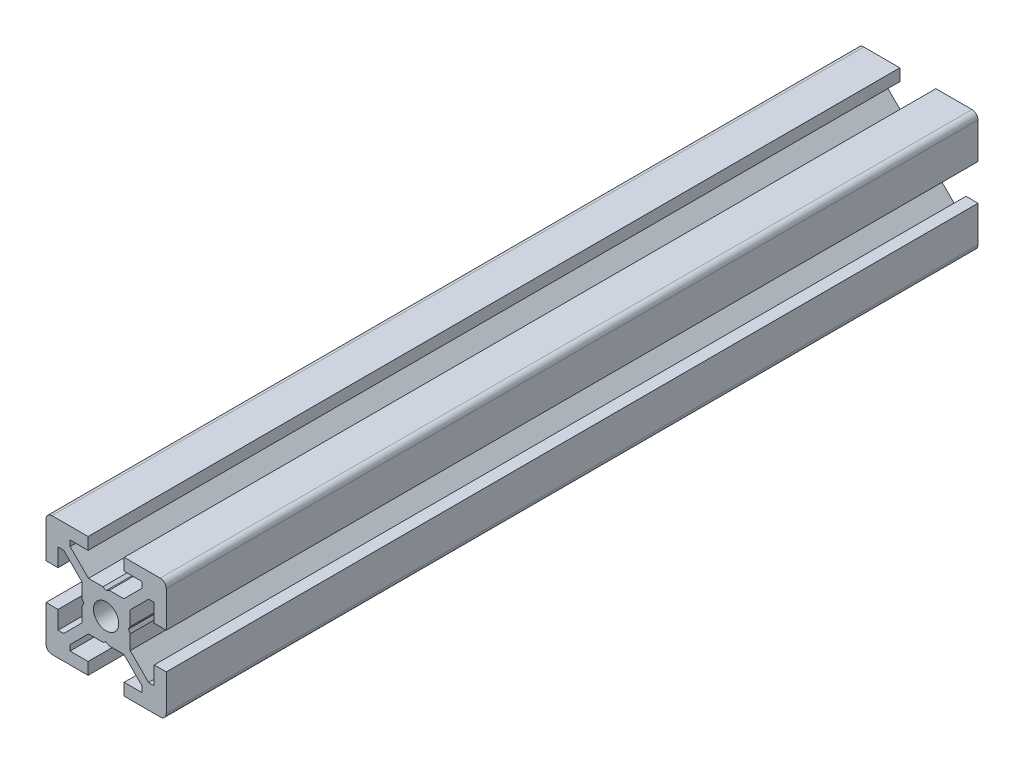
SolidWorks part; units mm, degrees
ref_plane "Front Plane" through (0, 0, 0) normal (0, 0, 1) x (1, 0, 0)
ref_plane "Top Plane" through (0, 0, 0) normal (0, 1, 0) x (1, 0, 0)
ref_plane "Right Plane" through (0, 0, 0) normal (1, 0, 0) x (0, 0, -1)
ref_plane "Plane1" through (0, 0, 0) normal (0, 0, 1) x (1, 0, 0)
sketch "Sketch1" plane through (0, 0, 0) normal (0, 0, 1) x (1, 0, 0)
  line L0 (-10, -3) -> (-10, -9)
  line L1 (-9, -10) -> (-3, -10)
  line L2 (-3, -10) -> (-3, -8)
  line L3 (-3, -8) -> (-6, -8)
  line L4 (-6, -8) -> (-6, -7.0607)
  line L5 (-6, -7.0607) -> (-2.9393, -4)
  line L6 (-2.9393, -4) -> (-0.5196, -4)
  line L7 (-0.5196, -4) -> (0, -3.7)
  line L8 (0, -3.7) -> (0.5196, -4)
  line L9 (0.5196, -4) -> (2.9393, -4)
  line L10 (2.9393, -4) -> (6, -7.0607)
  line L11 (6, -7.0607) -> (6, -8)
  line L12 (6, -8) -> (3, -8)
  line L13 (3, -8) -> (3, -10)
  line L14 (3, -10) -> (9, -10)
  line L15 (10, -9) -> (10, -3)
  line L16 (10, -3) -> (8, -3)
  line L17 (8, -3) -> (8, -6)
  line L18 (8, -6) -> (7.0607, -6)
  line L19 (7.0607, -6) -> (4, -2.9393)
  line L20 (4, -2.9393) -> (4, -0.5196)
  line L21 (4, -0.5196) -> (3.7, 0)
  line L22 (3.7, 0) -> (4, 0.5196)
  line L23 (4, 0.5196) -> (4, 2.9393)
  line L24 (4, 2.9393) -> (7.0607, 6)
  line L25 (7.0607, 6) -> (8, 6)
  line L26 (8, 6) -> (8, 3)
  line L27 (8, 3) -> (10, 3)
  line L28 (10, 3) -> (10, 9)
  line L29 (9, 10) -> (3, 10)
  line L30 (3, 10) -> (3, 8)
  line L31 (3, 8) -> (6, 8)
  line L32 (6, 8) -> (6, 7.0607)
  line L33 (6, 7.0607) -> (2.9393, 4)
  line L34 (2.9393, 4) -> (0.5196, 4)
  line L35 (0.5196, 4) -> (0, 3.7)
  line L36 (0, 3.7) -> (-0.5196, 4)
  line L37 (-0.5196, 4) -> (-2.9393, 4)
  line L38 (-2.9393, 4) -> (-6, 7.0607)
  line L39 (-6, 7.0607) -> (-6, 8)
  line L40 (-6, 8) -> (-3, 8)
  line L41 (-3, 8) -> (-3, 10)
  line L42 (-3, 10) -> (-9, 10)
  line L43 (-10, 9) -> (-10, 3)
  line L44 (-10, 3) -> (-8, 3)
  line L45 (-8, 3) -> (-8, 6)
  line L46 (-8, 6) -> (-7.0607, 6)
  line L47 (-7.0607, 6) -> (-4, 2.9393)
  line L48 (-4, 2.9393) -> (-4, 0.5196)
  line L49 (-4, 0.5196) -> (-3.7, 0)
  line L50 (-3.7, 0) -> (-4, -0.5196)
  line L51 (-4, -0.5196) -> (-4, -2.9393)
  line L52 (-4, -2.9393) -> (-7.0607, -6)
  line L53 (-7.0607, -6) -> (-8, -6)
  line L54 (-8, -6) -> (-8, -3)
  line L55 (-8, -3) -> (-10, -3)
  arc A0 (-10, -9) -> (-9, -10) centre (-9, -9) ccw
  arc A1 (9, -10) -> (10, -9) centre (9, -9) ccw
  arc A2 (10, 9) -> (9, 10) centre (9, 9) ccw
  arc A3 (-9, 10) -> (-10, 9) centre (-9, 9) ccw
extrude "Boss-Extrude1" add sketch "Sketch1" against normal blind 135
ref_plane "Plane2" through (0, 0, 0) normal (1, 0, 0) x (0, 0, -1)
sketch "Sketch2" plane through (0, 0, 0) normal (1, 0, 0) x (0, 0, -1)
  line L0 (0, 0) -> (0, 2.1)
  line L1 (0, 2.1) -> (135, 2.1)
  line L2 (135, 2.1) -> (135, 0)
  line L3 (135, 0) -> (0, 0)
  line L4 (135, 0) -> (0, 0) construction
revolve "Cut-Revolve1" cut sketch "Sketch2" angle 360 about L4 reverse direction yes
